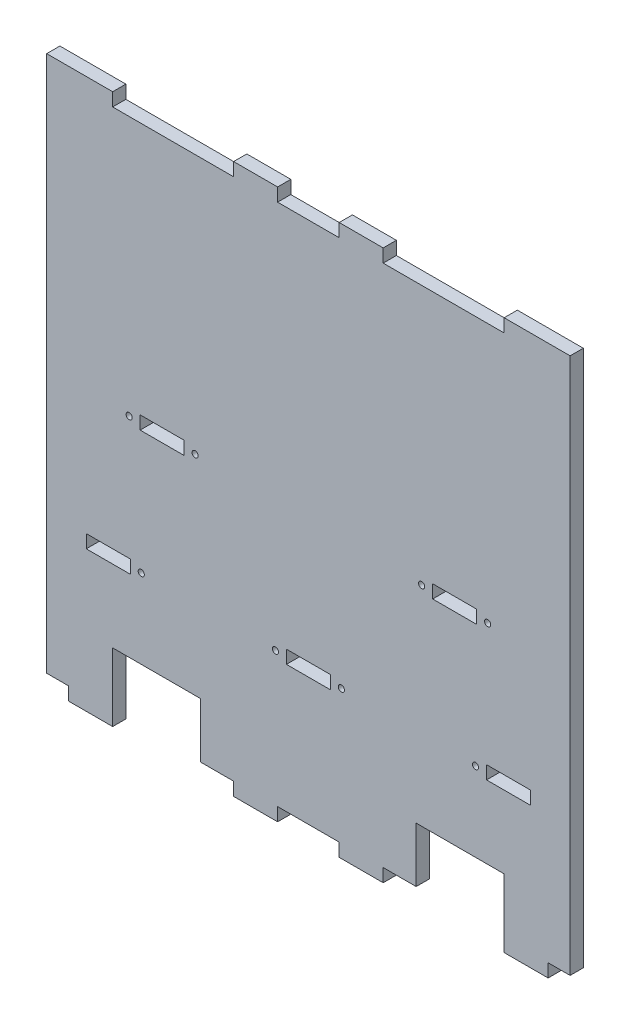
SolidWorks part; units mm, degrees
ref_plane "Plan de face" through (0, 0, 0) normal (0, 0, 1) x (1, 0, 0)
ref_plane "Plan de dessus" through (0, 0, 0) normal (0, 1, 0) x (1, 0, 0)
ref_plane "Plan de droite" through (0, 0, 0) normal (1, 0, 0) x (0, 0, -1)
sketch "Esquisse1" plane through (0, 0, 0) normal (0, 0, 1) x (1, 0, 0)
  line L1 (-109, 119) -> (109, 119)
  line L2 (-109, 119) -> (-109, -119)
  line L3 (-109, -119) -> (109, -119)
  line L4 (109, 119) -> (109, -119)
  line L5 (-101, -61) -> (-81, -61)
  line L6 (-101, -61) -> (-101, -55)
  line L7 (-101, -55) -> (-81, -55)
  line L8 (-81, -61) -> (-81, -55)
  line L9 (-10, -61) -> (10, -61)
  line L10 (-10, -61) -> (-10, -55)
  line L11 (-10, -55) -> (10, -55)
  line L12 (10, -61) -> (10, -55)
  line L13 (81, -61) -> (101, -61)
  line L14 (81, -61) -> (81, -55)
  line L15 (81, -55) -> (101, -55)
  line L16 (101, -61) -> (101, -55)
  line L17 (-76.5, 4) -> (-56.5, 4)
  line L18 (-76.5, 4) -> (-76.5, -2)
  line L19 (-76.5, -2) -> (-56.5, -2)
  line L20 (-56.5, 4) -> (-56.5, -2)
  line L21 (56.5, 4) -> (76.5, 4)
  line L22 (56.5, 4) -> (56.5, -2)
  line L23 (56.5, -2) -> (76.5, -2)
  line L24 (76.5, 4) -> (76.5, -2)
  dimension "D1" = 238
  dimension "D2" = 218
  dimension "D3" = 109
  dimension "D4" = 119
  dimension "D5" = 20
  dimension "D6" = 6
  dimension "D7" = 6
  dimension "D8" = 20
  dimension "D9" = 20
  dimension "D10" = 6
  dimension "D11" = 58
  dimension "D12" = 8
  dimension "D13" = 8
  dimension "D14" = 99
  dimension "D15" = 58
  dimension "D16" = 58
  dimension "D17" = 20
  dimension "D18" = 6
  dimension "D19" = 6
  dimension "D20" = 20
  dimension "D21" = 117
  dimension "D22" = 117
  dimension "D23" = 32.5
  dimension "D24" = 32.5
extrude "Boss.-Extru.1" add sketch "Esquisse1" along normal blind 6
sketch "Esquisse2" plane through (0, 0, 6) normal (0, 0, 1) x (1, 0, 0)
  line L0 (-109, -119) -> (109, -119) construction
  line L1 (-89, -119) -> (-49, -119)
  line L2 (-89, -119) -> (-89, -94)
  line L3 (-89, -94) -> (-49, -94)
  line L4 (-49, -119) -> (-49, -94)
  line L5 (-109, 119) -> (-109, -119) construction
  line L6 (49, -119) -> (89, -119)
  line L7 (49, -119) -> (49, -94)
  line L8 (49, -94) -> (89, -94)
  line L9 (89, -119) -> (89, -94)
  line L10 (109, -119) -> (109, 119) construction
  dimension "D1" = 40
  dimension "D2" = 20
  dimension "D3" = 40
  dimension "D4" = 20
  dimension "D5" = 25
  dimension "D6" = 25
extrude "Enlèv. mat.-Extru.1" cut sketch "Esquisse2" against normal blind 6
sketch "Esquisse3" plane through (0, 0, 6) normal (0, 0, 1) x (1, 0, 0)
  line L0 (0, 157.5653) -> (0, -190.6765) construction
  line L1 (-89, -125) -> (-109, -125)
  line L2 (-89, -125) -> (-89, -119)
  line L3 (-89, -119) -> (-109, -119)
  line L4 (-109, -125) -> (-109, -119)
  line L5 (-49, -119) -> (49, -119) construction
  line L6 (-34, -119) -> (-14, -119)
  line L7 (-34, -119) -> (-34, -125)
  line L8 (-34, -125) -> (-14, -125)
  line L9 (-14, -119) -> (-14, -125)
  line L10 (-49, -119) -> (-49, -94) construction
  line L11 (109, -125) -> (109, -119)
  line L12 (89, -119) -> (109, -119)
  line L13 (89, -125) -> (89, -119)
  line L14 (89, -125) -> (109, -125)
  line L15 (14, -119) -> (14, -125)
  line L16 (34, -125) -> (14, -125)
  line L17 (34, -119) -> (34, -125)
  line L18 (34, -119) -> (14, -119)
  line L19 (198.2674, 0) -> (-212.4835, 0) construction
  line L20 (0, -157.5653) -> (0, 190.6765) construction
  line L21 (34, 125) -> (14, 125)
  line L22 (14, 119) -> (14, 125)
  line L23 (89, 125) -> (109, 125)
  line L24 (89, 125) -> (89, 119)
  line L25 (89, 119) -> (109, 119)
  line L26 (109, 125) -> (109, 119)
  line L27 (-14, 119) -> (-14, 125)
  line L28 (-34, 125) -> (-14, 125)
  line L29 (-34, 119) -> (-34, 125)
  line L30 (-34, 119) -> (-14, 119)
  line L31 (-109, 125) -> (-109, 119)
  line L32 (-89, 119) -> (-109, 119)
  line L33 (-89, 125) -> (-89, 119)
  line L34 (-89, 125) -> (-109, 125)
  line L35 (34, 119) -> (14, 119)
  line L36 (34, 119) -> (34, 125)
  dimension "D1" = 6
  dimension "D2" = 20
  dimension "D3" = 6
  dimension "D4" = 15
  dimension "D5" = 20
extrude "Boss.-Extru.3" add sketch "Esquisse3" against normal blind 6
sketch "Esquisse4" plane through (0, 0, 6) normal (0, 0, 1) x (1, 0, 0)
  line L0 (-111.0944, 1) -> (126.4062, 1) construction
  line L1 (116.6655, -58) -> (-122.9189, -58) construction
  line L2 (76.5, -2) -> (76.5, 4) construction
  line L3 (0, 153.5677) -> (0, -173.1111) construction
  line L4 (56.5, 4) -> (56.5, -2) construction
  line L5 (81, -55) -> (81, -61) construction
  line L6 (10, -61) -> (10, -55) construction
  line L7 (-10, -55) -> (-10, -61) construction
  circle A0 centre (-15, -58) radius 1.4
  circle A1 centre (-76, -58) radius 1.4
  circle A2 centre (51.5, 1) radius 1.4
  circle A3 centre (81.5, 1) radius 1.4
  circle A4 centre (76, -58) radius 1.4
  circle A5 centre (15, -58) radius 1.4
  circle A6 centre (-81.5, 1) radius 1.4
  circle A7 centre (-51.5, 1) radius 1.4
  dimension "D1" = 5
  dimension "D2" = 5
  dimension "D3" = 2.8
  dimension "D4" = 2.8
  dimension "D5" = 5
  dimension "D6" = 5
  dimension "D7" = 2.8
  dimension "D8" = 2.8
  dimension "D9" = 2.8
  dimension "D10" = 5
extrude "Enlèv. mat.-Extru.2" cut sketch "Esquisse4" against normal blind 6
sketch "Esquisse5" plane through (0, 0, 6) normal (0, 0, 1) x (1, 0, 0)
  line L0 (-109, 125) -> (-109, -119)
  line L1 (-109, 125) -> (-119, 125)
  line L2 (-109, -119) -> (-119, -119)
  line L3 (-119, 125) -> (-119, -119)
  line L5 (109, -119) -> (109, 125)
  line L6 (109, -119) -> (119, -119)
  line L7 (109, 125) -> (119, 125)
  line L8 (119, -119) -> (119, 125)
  dimension "D1" = 10
  dimension "D2" = 10
  dimension "D3" = 244
  dimension "D4" = 244
extrude "Boss.-Extru.4" add sketch "Esquisse5" against normal blind 6
equation "\"D3@Esquisse1\"=\"D2@Esquisse1\"/2"
equation "\"D4@Esquisse1\"=\"D1@Esquisse1\"/2"
